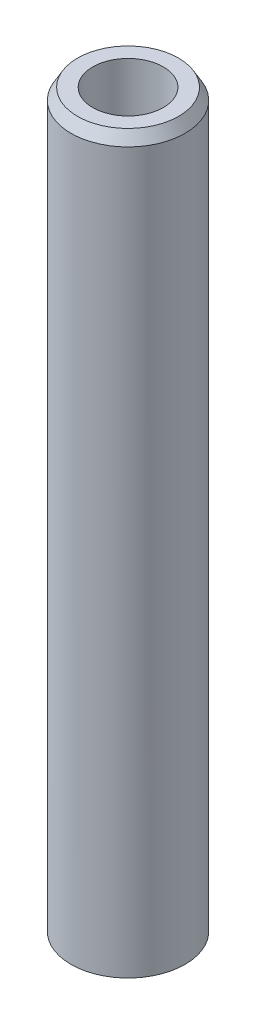
SolidWorks part; units mm, degrees
ref_plane "Front Plane" through (0, 0, 0) normal (0, 0, 1) x (1, 0, 0)
ref_plane "Top Plane" through (0, 0, 0) normal (0, 1, 0) x (1, 0, 0)
ref_plane "Right Plane" through (0, 0, 0) normal (1, 0, 0) x (0, 0, -1)
sketch "Sketch1" plane through (0, 0, 0) normal (0, 1, 0) x (1, 0, 0)
  circle A0 centre (0, 0) radius 25
  dimension "SHAFT_OD" = 50
extrude "Boss-Extrude1" add sketch "Sketch1" along normal blind 323.0195
sketch "Sketch2" plane through (0, 0, 0) normal (0, 1, 0) x (1, 0, 0)
  circle A0 centre (0, 0) radius 15.4528
  dimension "BORE_D" = 30.9055
extrude "Cut-Extrude1" cut sketch "Sketch2" along normal through all
chamfer "Chamfer1" distance 4.9865 angle 30 2 edges at (0, 323.0195, 25) (0, 0, 25) first distance on face at (0, 323.0195, 25) first distance on face at (0, 0, 15.4528)
